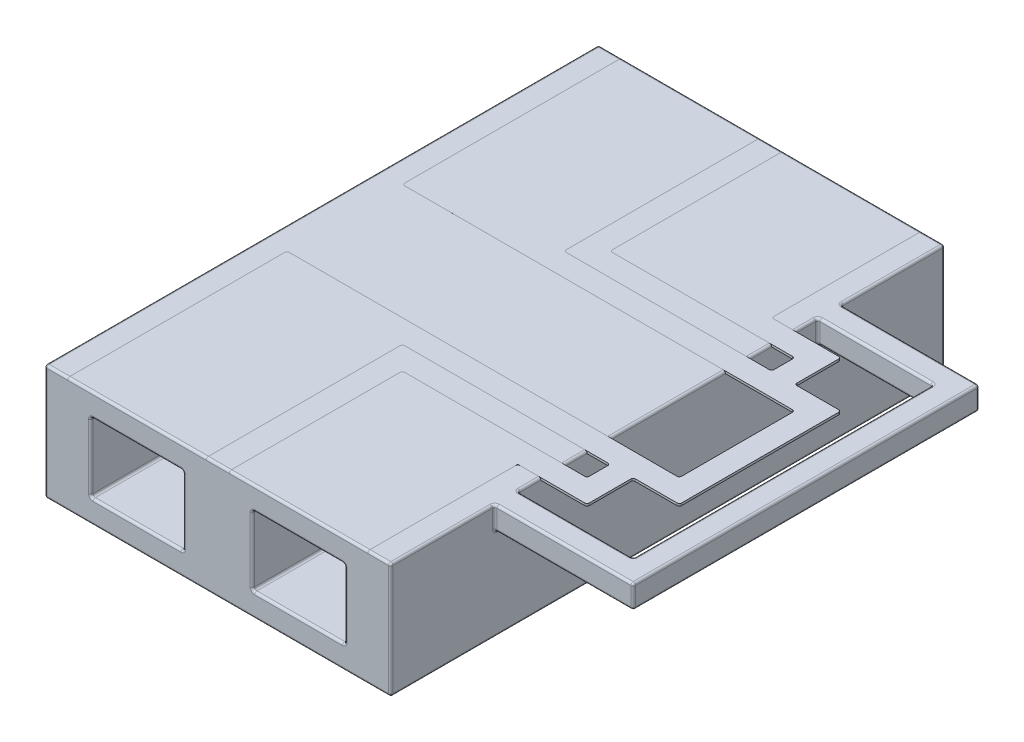
SolidWorks part; units mm, degrees
other "temp_4T_sensing"
other "temp_4T_sensing_elem"
ref_plane "Front Plane" through (0, 0, 0) normal (0, 0, 1) x (1, 0, 0)
ref_plane "Top Plane" through (0, 0, 0) normal (0, 1, 0) x (1, 0, 0)
ref_plane "Right Plane" through (0, 0, 0) normal (1, 0, 0) x (0, 0, -1)
sketch "Sketch: Shroud Surfaces" plane through (0, 0, 0) normal (0, 1, 0) x (1, 0, 0)
  line L33 (15, 7.5) -> (21, 7.5)
  line L40 (15, 7.5) -> (15, 12)
  line L41 (15, 12) -> (0, 12)
  line L42 (0, 12) -> (0, -12)
  line L44 (0, -12) -> (15, -12)
  line L45 (15, -12) -> (15, -7.5)
  line L48 (21, 7.5) -> (21, -7.5)
  line L49 (21, -7.5) -> (15, -7.5)
  line L50 (15, -7.5) -> (15, -6.5) construction
  line L51 (15, -6.5) -> (20, -6.5)
  line L52 (15, -6.5) -> (15, 6.5)
  line L53 (15, 6.5) -> (20, 6.5)
  line L54 (20, -6.5) -> (20, 6.5)
  line L55 (15, 6.5) -> (15, 7.5) construction
extrude "Shroud Surfaces" add sketch "Sketch: Shroud Surfaces" against normal blind 1 separate body contours L40 L41 L42 L44 L45 region at (8.2662, 0, 0)
sketch "Sketch: Mount" plane through (0, -1, 0) normal (0, -1, 0) x (1, 0, 0)
  line L0 (0, -12) -> (0, 12) construction
  line L1 (0, -12) -> (15, -12)
  line L2 (0, -12) -> (0, 12)
  line L3 (0, 12) -> (15, 12)
  line L4 (15, -12) -> (15, 12)
extrude "Mount" add sketch "Sketch: Mount" along normal blind 4
fillet "Body Fillets" radius 0.1 36 edges at (0, 0, 0) (7.5, 0, -12) (7.5, 0, 12) (0, -2.5, 12) (0, -2.5, -12) (15, -2.5, 12) (15, -2.5, -12) (15, -5, 0) (7.5, -5, -12) (0, -5, 0) (7.5, -5, 12) (15, 0, -9.75) (15, 0, 9.75) (15, -0.5, 6.5) (17.5, -1, 6.5) (15, -1, -7) (15, -1, 7) (20, -1, 0) (18, -1, -7.5) (15, -0.5, -7.5) (15, -0.5, -6.5) (21, -0.5, -7.5) (15, -0.5, 7.5) (21, -1, 0) (21, -0.5, 7.5) (18, -1, 7.5) (20, -0.5, 6.5) (17.5, -1, -6.5) (20, -0.5, -6.5) (17.5, 0, 6.5) (17.5, 0, -6.5) (20, 0, 0) (15, 0, 0) (18, 0, -7.5) (21, 0, 0) (18, 0, 7.5)
sketch "Sketch: Conductive Traces" plane through (0, 0, 0) normal (0, 1, 0) x (1, 0, 0)
  line L21 (18, -2.5) -> (1, -2.5)
  line L24 (14, -12) -> (14, -5.5)
  line L28 (14, 5.5) -> (14, 12)
  line L31 (1, 2.5) -> (18, 2.5)
  line L33 (16, -3.5) -> (16, -4.5)
  line L39 (21, 7.5) -> (15, 7.5) construction
  line L40 (15, 7.5) -> (15, 12) construction
  line L41 (15, 12) -> (0, 12) construction
  line L44 (0, -12) -> (15, -12) construction
  line L45 (15, -12) -> (15, -7.5) construction
  line L46 (15, -7.5) -> (21, -7.5) construction
  line L48 (16, 3.5) -> (16, 4.5)
  line L49 (8, -12) -> (8, -4.5)
  line L50 (8, -4.5) -> (16, -4.5)
  line L55 (18, -2.5) -> (18, 2.5)
  line L61 (16, 4.5) -> (8, 4.5)
  line L62 (8, 4.5) -> (8, 12)
  line L63 (1, -2.5) -> (1, -12)
  line L64 (1, 2.5) -> (1, 12)
  line L65 (16, -3.5) -> (7, -3.5)
  line L68 (7, -3.5) -> (7, -12)
  line L69 (16, 3.5) -> (7, 3.5)
  line L72 (7, 3.5) -> (7, 12)
  line L73 (14, 5.5) -> (17, 5.5)
  line L74 (0, 12) -> (0, -12) construction
  line L75 (1, -12) -> (7, -12)
  line L76 (8, -12) -> (14, -12)
  line L77 (1, 12) -> (7, 12)
  line L78 (8, 12) -> (14, 12)
  line L79 (17, 5.5) -> (17, 3.5)
  line L80 (17, 3.5) -> (19, 3.5)
  line L81 (19, 3.5) -> (19, -3.5)
  line L82 (19, -3.5) -> (17, -3.5)
  line L84 (17, -3.5) -> (17, -5.5)
  line L85 (17, -5.5) -> (14, -5.5)
  line L86 (21, 7.5) -> (21, -7.5) construction
  line L88 (15, -6.5) -> (20, -6.5) construction
  line L89 (15, -6.5) -> (15, 6.5) construction
  line L90 (15, 6.5) -> (20, 6.5) construction
  line L91 (20, -6.5) -> (20, 6.5) construction
extrude "Space for Conductive Traces" cut sketch "Sketch: Conductive Traces" against normal blind 0.1
fillet "Space for Conductive Traces Fillets" radius 0.1 8 edges at (8, -0.05, 4.5) (8, -0.05, -4.5) (1, -0.05, -2.5) (1, -0.05, 2.5) (14, -0.05, -5.5) (14, -0.05, 5.5) (7, -0.05, 3.5) (7, -0.05, -3.5)
extrude "Conductive Traces" add sketch "Conductive Traces Sketch<5>" against normal blind 0.1 separate body
sketch "Conductive Traces Sketch<5>" plane through (0, 0, 0) normal (0, 1, 0) x (1, 0, 0) same geometry as "Sketch: Conductive Traces"
fillet "Conductive Traces Fillets" radius 0.1 19 edges at (18, -0.05, -2.5) (16, -0.05, 4.5) (16, -0.05, -3.5) (16, -0.05, 3.5) (16, -0.05, -4.5) (8, -0.05, -4.5) (1, -0.05, -2.5) (8, -0.05, 4.5) (1, -0.05, 2.5) (14, -0.05, -5.5) (17, -0.05, 3.5) (18, -0.05, 2.5) (17, -0.05, 5.5) (19, -0.05, 3.5) (17, -0.05, -3.5) (19, -0.05, -3.5) (17, -0.05, -5.5) (7, -0.05, 3.5) (7, -0.05, -3.5)
fillet "Electrical Contacts Fillets" radius 0.1 4 edges at (11, 0, -12) (4, 0, -12) (11, 0, 12) (4, 0, 12)
sketch "Sketch0" plane through (0, 0, 0) normal (0, 1, 0) x (1, 0, 0)
  line L1 (2, 12) -> (6, 12)
  line L2 (2, 12) -> (2, 7)
  line L3 (2, 7) -> (6, 7)
  line L4 (6, 12) -> (6, 7)
  line L6 (9, 12) -> (13, 12)
  line L7 (9, 12) -> (9, 7)
  line L8 (9, 7) -> (13, 7)
  line L9 (13, 12) -> (13, 7)
  line L10 (9, -7) -> (13, -7)
  line L11 (9, -7) -> (9, -12)
  line L12 (9, -12) -> (13, -12)
  line L13 (13, -7) -> (13, -12)
  line L14 (2, -7) -> (6, -7)
  line L15 (2, -7) -> (2, -12)
  line L16 (2, -12) -> (6, -12)
  line L17 (6, -7) -> (6, -12)
extrude "Cut-Extrude0" cut sketch "Sketch0" against normal blind 3 from offset 1 offset against normal yes
fillet "Fillet0" radius 0.1 48 edges at (6, -2.5, -12) (2, -2.5, -12) (13, -2.5, -12) (9, -2.5, -12) (9, -2.5, 12) (13, -2.5, 12) (2, -2.5, 12) (6, -2.5, 12) (6, -2.5, -7) (2, -2.5, -7) (4, -1, -7) (6, -1, -9.5) (4, -1, -12) (2, -1, -9.5) (13, -2.5, -7) (9, -2.5, -7) (11, -1, -7) (13, -1, -9.5) (11, -1, -12) (9, -1, -9.5) (9, -2.5, 7) (13, -2.5, 7) (2, -2.5, 7) (6, -2.5, 7) (11, -1, 12) (13, -1, 9.5) (11, -1, 7) (9, -1, 9.5) (4, -1, 12) (6, -1, 9.5) (4, -1, 7) (2, -1, 9.5) (4, -4, -7) (11, -4, -7) (11, -4, 7) (4, -4, 7) (11, -4, -12) (4, -4, -12) (4, -4, 12) (11, -4, 12) (13, -4, -9.5) (2, -4, -9.5) (9, -4, -9.5) (6, -4, -9.5) (6, -4, 9.5) (2, -4, 9.5) (9, -4, 9.5) (13, -4, 9.5)
